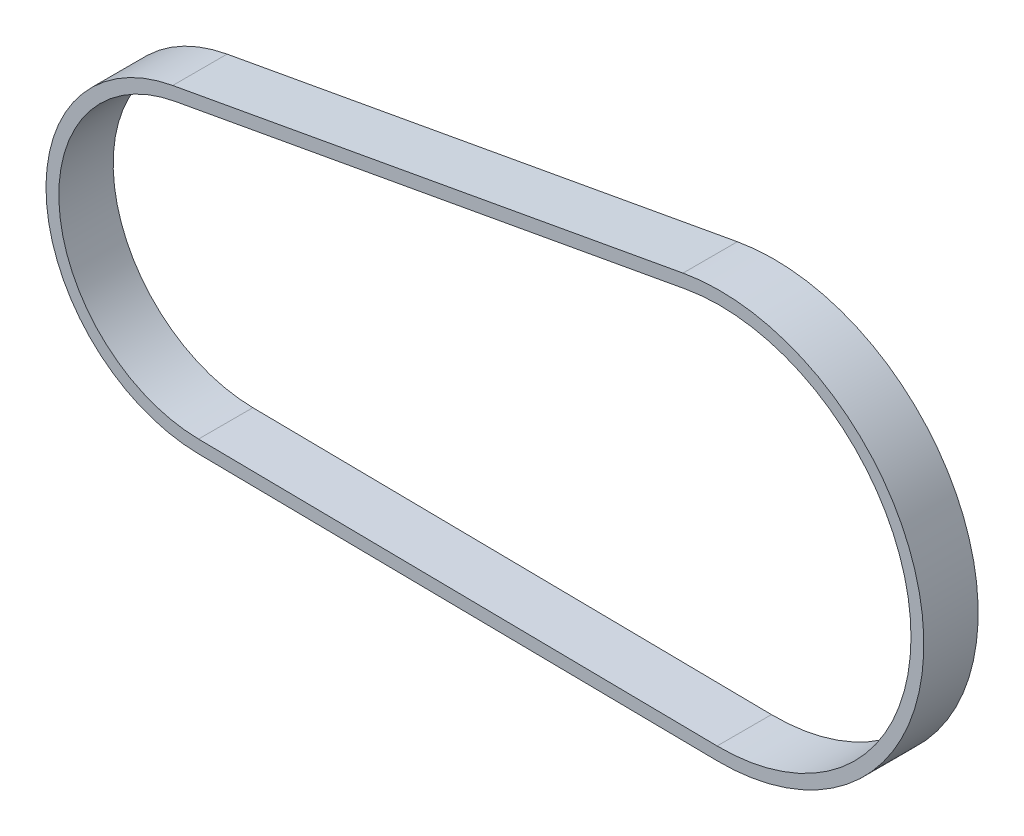
SolidWorks part; units mm, degrees
ref_plane "Front Plane" through (0, 0, 0) normal (0, 0, 1) x (1, 0, 0)
ref_plane "Top Plane" through (0, 0, 0) normal (0, 1, 0) x (1, 0, 0)
ref_plane "Right Plane" through (0, 0, 0) normal (1, 0, 0) x (0, 0, -1)
sketch "Sketch2" plane through (0, 0, 0) normal (0, 0, 1) x (1, 0, 0)
  line L0 (0, 0) -> (1, 0) construction
  line L1 (0, 0) -> (0, 1) construction
  line L4 (60.3751, -18.7941) -> (-0.2266, -18.0326)
  line L5 (-3.222, 17.7438) -> (56.4095, 28.5719)
  arc A2 (56.4095, 28.5719) -> (60.3751, -18.7941) centre (60.6752, 5.08) cw
  arc A3 (-0.2266, -18.0326) -> (-3.222, 17.7438) centre (0, 0) cw
extrude "Extrude-Thin1" add sketch "Sketch2" against normal mid plane 6.35 thin thin type one direction reverse wall 1.5
